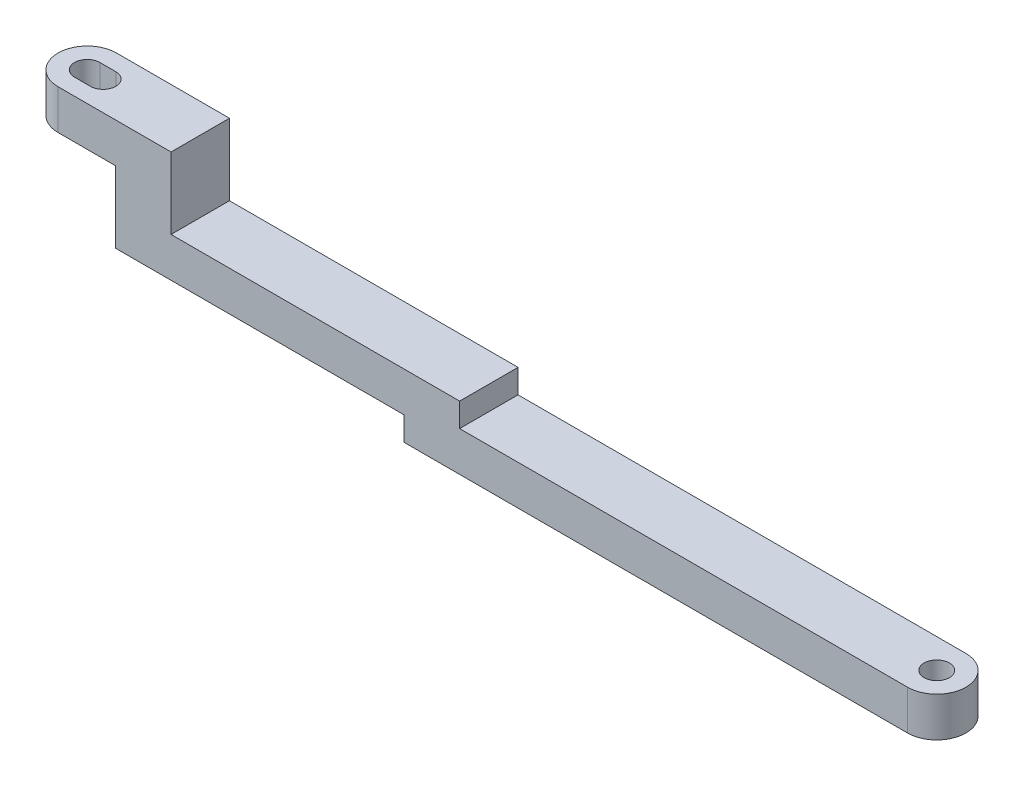
SolidWorks part; units mm, degrees
note: The reader was unsure of these and kept them because the rebuilt part matched: shared geometry of "Sketch2<3>", "Sketch2<4>", "Sketch3<3>", "Sketch3<4>".
ref_plane "Front Plane" through (0, 0, 0) normal (0, 0, 1) x (1, 0, 0)
ref_plane "Top Plane" through (0, 0, 0) normal (0, 1, 0) x (1, 0, 0)
ref_plane "Right Plane" through (0, 0, 0) normal (1, 0, 0) x (0, 0, -1)
sketch "Sketch1" plane through (0, 0, 0) normal (0, 1, 0) x (1, 0, 0)
  line L0 (0, 0) -> (107, 0) construction
  line L1 (0, 3.68) -> (107, 3.68)
  line L2 (0, -3.68) -> (107, -3.68)
  line L3 (0, 0) -> (2, 0) construction
  line L4 (0, 1.6) -> (2, 1.6)
  line L5 (0, -1.6) -> (2, -1.6)
  arc A0 (0, 3.68) -> (0, -3.68) centre (0, 0) ccw
  arc A1 (107, -3.68) -> (107, 3.68) centre (107, 0) ccw
  arc A2 (0, 1.6) -> (0, -1.6) centre (0, 0) ccw
  arc A3 (2, -1.6) -> (2, 1.6) centre (2, 0) ccw
  circle A4 centre (107, 0) radius 1.6
  point P3 (53.5, 0)
  point P10 (1, 0)
  dimension "D4" = 1.6
  dimension "D5" = 3.2
  dimension "D1" = 7.36
  dimension "D2" = 107
  dimension "D3" = 2
extrude "Boss-Extrude1" add sketch "Sketch1" along normal blind 5
sketch "Sketch2" plane through (0, 0, 0) normal (0, -1, 0) x (1, 0, 0)
  line L0 (0, 1.6) -> (2, 1.6) construction
  line L1 (2, -1.6) -> (0, -1.6) construction
  line L2 (0, -3.68) -> (107, -3.68)
  line L3 (107, 3.68) -> (0, 3.68)
  line L4 (0, -3.68) -> (107, -3.68)
  line L5 (107, 3.68) -> (0, 3.68)
  line L6 (0, 1.6) -> (2, 1.6)
  line L7 (2, -1.6) -> (0, -1.6)
  line L8 (7.2341, 3.68) -> (7.2341, -3.68)
  line L10 (14.2341, 3.68) -> (14.2341, -3.68)
  arc A0 (0, 1.6) -> (0, -1.6) centre (0, 0) ccw construction
  arc A1 (2, -1.6) -> (2, 1.6) centre (2, 0) ccw construction
  arc A2 (0, 3.68) -> (0, -3.68) centre (0, 0) ccw
  arc A3 (107, -3.68) -> (107, 3.68) centre (107, 0) ccw
  arc A4 (0, 3.68) -> (0, -3.68) centre (0, 0) ccw
  arc A5 (107, -3.68) -> (107, 3.68) centre (107, 0) ccw
  arc A6 (0, 1.6) -> (0, -1.6) centre (0, 0) ccw
  arc A7 (2, -1.6) -> (2, 1.6) centre (2, 0) ccw
  dimension "D1" = 0
  dimension "D2" = 7
extrude "Boss-Extrude2" add sketch "Sketch2" along normal blind 5 from surface separate body
extrude "Cut-Extrude1" cut sketch "Sketch2<3>" against normal up to surface (5 mm away)
sketch "Sketch2<3>" plane through (0, 0, 0) normal (0, -1, 0) x (1, 0, 0) same geometry as "Sketch2"
extrude "Boss-Extrude3" add sketch "Sketch2<4>" against normal up to surface (14 mm away) up to face at (2.6971, 14, 0)
sketch "Sketch2<4>" plane through (0, 0, 0) normal (0, -1, 0) x (1, 0, 0) same geometry as "Sketch2"
sketch "Sketch3" plane through (0, 0, 0) normal (0, -1, 0) x (1, 0, 0)
  line L1 (107, 3.68) -> (7.2341, 3.68) construction
  line L2 (7.2341, -3.68) -> (107, -3.68) construction
  line L3 (107, 3.68) -> (7.2341, 3.68)
  line L4 (7.2341, -3.68) -> (107, -3.68)
  line L5 (50.5827, -3.68) -> (50.5827, 3.68)
  line L6 (43.5827, -3.68) -> (43.5827, 3.68)
  circle A0 centre (107, 0) radius 3.68
  arc A1 (107, -3.68) -> (107, 3.68) centre (107, 0) ccw construction
  arc M3 (107, -3.68) -> (107, 3.68) centre (107, 0) ccw
  line M4 (107, 3.68) -> (7.2341, 3.68)
  circle M6 centre (107, 0) radius 1.6
  dimension "D1" = 7
extrude "Boss-Extrude4" add sketch "Sketch3" along normal blind 5 from surface at -2 separate body contours A0 L5 L4 M4 | A0 M3 M6
extrude "Cut-Extrude2" cut sketch "Sketch3<3>" against normal through all contours A0 M3 M6 | A0 L5 L4 M4
sketch "Sketch3<3>" plane through (0, 0, 0) normal (0, -1, 0) x (1, 0, 0) same geometry as "Sketch3"
extrude "Boss-Extrude5" add sketch "Sketch3<4>" along normal up to surface (3 mm away) contours L6 L4 L5 L3 up to face at (79.7113, -3, 0)
sketch "Sketch3<4>" plane through (0, 0, 0) normal (0, -1, 0) x (1, 0, 0) same geometry as "Sketch3"
